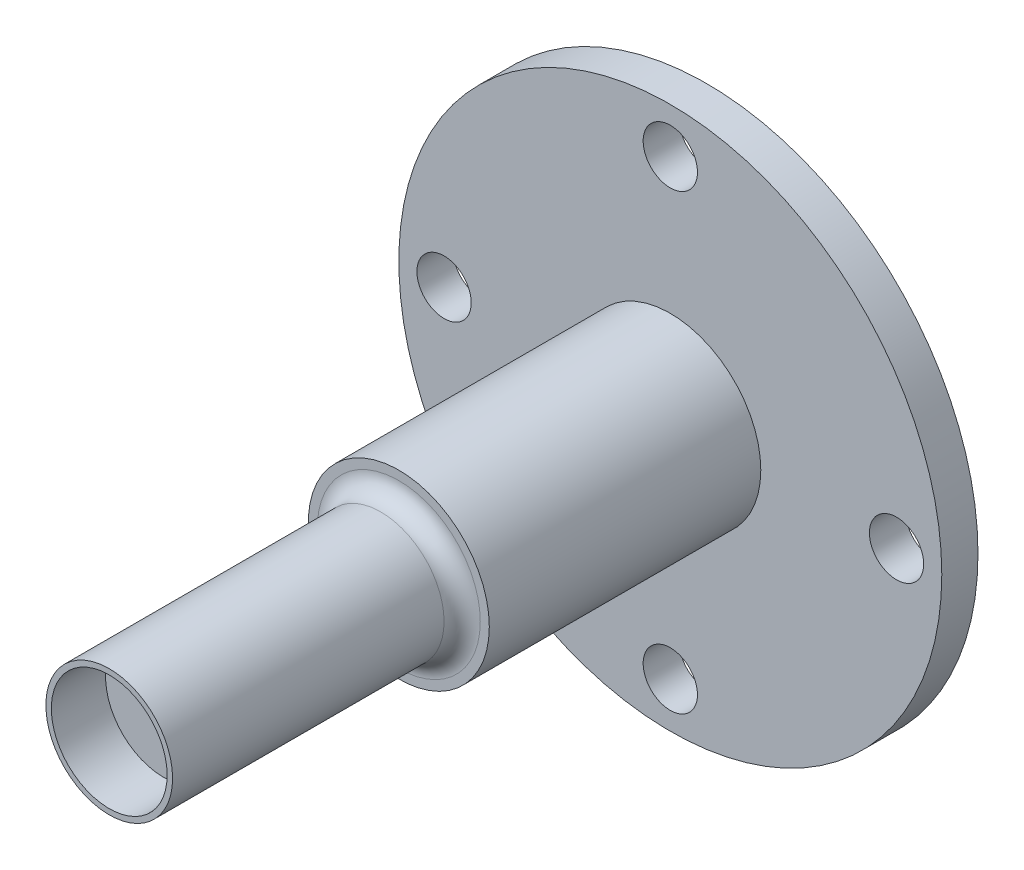
SolidWorks part; units mm, degrees
ref_plane "Front Plane" through (0, 0, 0) normal (0, 0, 1) x (1, 0, 0)
ref_plane "Top Plane" through (0, 0, 0) normal (0, 1, 0) x (1, 0, 0)
ref_plane "Right Plane" through (0, 0, 0) normal (1, 0, 0) x (0, 0, -1)
sketch "Sketch1" plane through (0, 0, 0) normal (0, 0, 1) x (1, 0, 0)
  circle A0 centre (0, 0) radius 12.5 construction
  circle A1 centre (0, 12.5) radius 1.5
  circle A2 centre (12.5, 0) radius 1.5
  circle A3 centre (0, -12.5) radius 1.5
  circle A4 centre (-12.5, 0) radius 1.5
  circle A5 centre (0, 0) radius 5
  circle A6 centre (0, 0) radius 15
  circle A7 centre (0, 0) radius 3.5
  circle A8 centre (0, 0) radius 3.2
  point P14 (0, 0)
  dimension "D1" = 25
  dimension "D2" = 3
  dimension "D4" = 10
  dimension "D5" = 30
  dimension "D6" = 7
  dimension "D7" = 6.4
  dimension "D3" = 4
extrude "Boss-Extrude1" add sketch "Sketch1" along normal blind 2 contours A6 A1 A2 A3 A4 A5 region at (-14.5757, 0, 0)
extrude "Boss-Extrude2" add sketch "Sketch1<3>" along normal blind 17 contours A5 A7 | A7 A8 | A8 region at (-4.8586, 0, 0) region at (-3.401, 0, 0) region at (0, 0, 0)
sketch "Sketch1<3>" plane through (0, 0, 0) normal (0, 0, 1) x (1, 0, 0) same geometry as "Sketch1"
extrude "Boss-Extrude3" add sketch "Sketch1<4>" along normal blind 16 from surface contours A7 A8 region at (-3.401, 0, 0) starting at face at (5, 0, 17)
sketch "Sketch1<4>" plane through (0, 0, 0) normal (0, 0, 1) x (1, 0, 0) same geometry as "Sketch1"
sketch "Sketch2" plane through (0, 0, 17) normal (0, 0, 1) x (1, 0, 0)
  circle A1 centre (0, 0) radius 3.2
  circle A2 centre (0, 0) radius 3.2
  dimension "D1" = 0
extrude "Boss-Extrude4" add sketch "Sketch2" along normal offset from surface (13 mm away) 3 up to face at (3.5, 0, 33)
fillet "Fillet1" radius 1 1 edges at (3.5, 0, 17)
